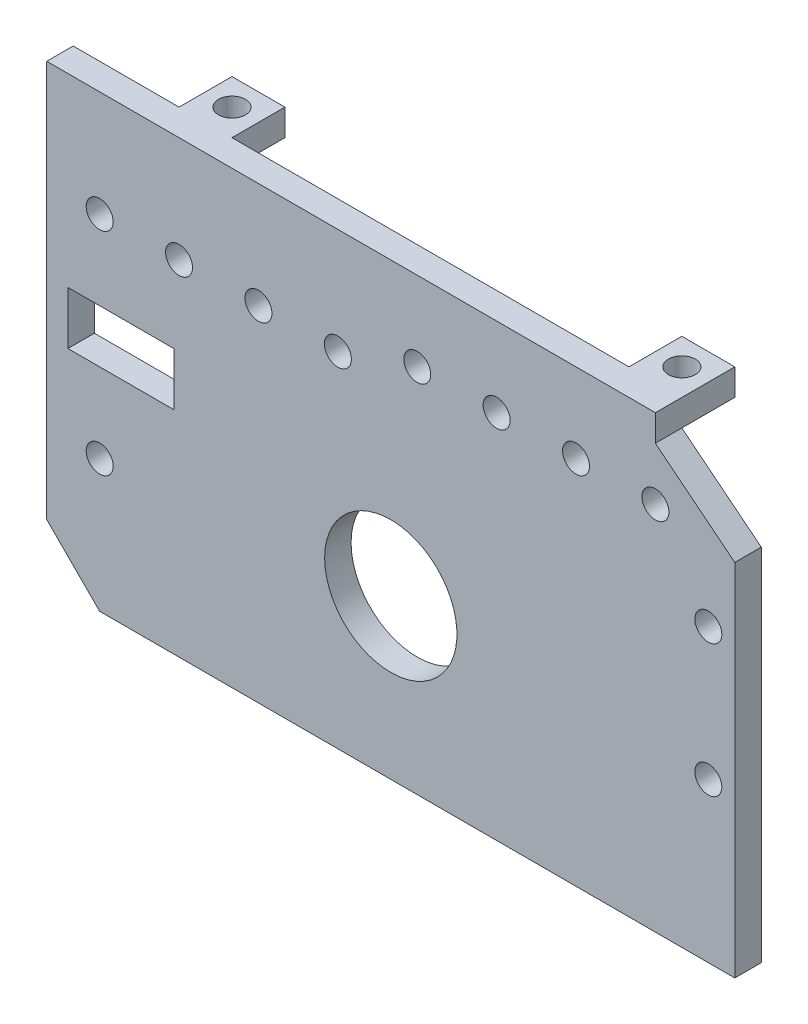
SolidWorks part; units mm, degrees
material "PLA+ esun"
ref_plane "Front Plane" through (0, 0, 0) normal (0, 0, 1) x (1, 0, 0)
ref_plane "Top Plane" through (0, 0, 0) normal (0, 1, 0) x (1, 0, 0)
ref_plane "Right Plane" through (0, 0, 0) normal (1, 0, 0) x (0, 0, -1)
sketch "Sketch1" plane through (0, 0, 0) normal (0, 0, 1) x (1, 0, 0)
  line L1 (-80, 42.5) -> (80, 42.5)
  line L2 (-80, 42.5) -> (-80, -42.5)
  line L3 (-80, -42.5) -> (80, -42.5)
  line L4 (80, 42.5) -> (80, -42.5)
  line L5 (-80, 42.5) -> (80, -42.5) construction
  line L6 (-80, -42.5) -> (80, 42.5) construction
  circle A0 centre (0, 0) radius 5
  point P0 (0, 0)
  dimension "D3" = 10
  dimension "D1" = 85
  dimension "D2" = 160
extrude "Boss-Extrude1" add sketch "Sketch1" along normal blind 5
sketch "Sketch3" plane through (0, 0, 5) normal (0, 0, 1) x (1, 0, 0)
  line L0 (-80, -42.5) -> (80, -42.5) construction
  line L1 (-80, 42.5) -> (-50, 42.5)
  line L2 (-80, 42.5) -> (-80, -42.5)
  line L3 (-80, -42.5) -> (-50, -42.5)
  line L4 (-50, 42.5) -> (-50, -42.5)
  dimension "D1" = 30
extrude "Cut-Extrude2" cut sketch "Sketch3" against normal blind 15
sketch "Sketch5" plane through (0, 0, 5) normal (0, 0, 1) x (1, 0, 0)
  line L0 (80, 42.5) -> (-50, 42.5) construction
  line L2 (80, -42.5) -> (80, 42.5) construction
  circle A0 centre (65, 27.5) radius 2.55
  circle A1 centre (50, 27.5) radius 2.55
  circle A2 centre (35, 27.5) radius 2.55
  circle A3 centre (20, 27.5) radius 2.55
  circle A8 centre (-40, 27.5) radius 2.55 [skipped]
  circle A9 centre (-25, 27.5) radius 2.55 [skipped]
  circle A10 centre (-10, 27.5) radius 2.55 [skipped]
  circle A11 centre (5, 27.5) radius 2.55 [skipped]
  circle A12 centre (5, 22.5) radius 2.55
  circle A13 centre (-10, 22.5) radius 2.55
  circle A14 centre (-25, 22.5) radius 2.55
  circle A15 centre (-40, 22.5) radius 2.55
  circle A17 centre (-40, -17.5) radius 2.55
  dimension "D1" = 5.1
  dimension "D2" = 15
  dimension "D3" = 15
  dimension "D5" = 15
  dimension "D6" = 5.1
  dimension "D7" = 15
  dimension "D8" = 20
  dimension "D10" = 2
  dimension "D4" = 8
  dimension "D9" = 4
extrude "Cut-Extrude3" cut sketch "Sketch5" against normal blind 15
chamfer "Chamfer1" distance 10 angle 45 1 edges at (-50, -42.5, 2.5)
sketch "Sketch6" plane through (0, 0, 0) normal (0, 0, -1) x (-1, 0, 0)
  line L0 (40, -42.5) -> (-80, -42.5) construction
  line L1 (-80, -42.5) -> (-65, -42.5)
  line L2 (-80, -42.5) -> (-80, -37.5)
  line L3 (-80, -37.5) -> (-65, -37.5)
  line L4 (-65, -42.5) -> (-65, -37.5)
  line L5 (-65, -37.5) -> (-55, -37.5)
  line L6 (-65, -37.5) -> (-65, -42.5)
  line L7 (-65, -42.5) -> (-55, -42.5)
  line L8 (-55, -37.5) -> (-55, -42.5)
  line L15 (50, -32.5) -> (50, 42.5) construction
  line L16 (30, -42.5) -> (20, -42.5)
  line L17 (30, -42.5) -> (30, -37.5)
  line L18 (30, -37.5) -> (20, -37.5)
  line L19 (20, -42.5) -> (20, -37.5)
  line M14 (-80, -42.5) -> (40, -42.5)
  dimension "D1" = 15
  dimension "D2" = 5
  dimension "D3" = 10
  dimension "D4" = 5
  dimension "D5" = 10
  dimension "D6" = 20
extrude "Boss-Extrude2" add sketch "Sketch6" along normal blind 10 contours L8 L5 L4 M14 | L19 L17 L18 M14 region at (-25, -40, 0) region at (60, -40, 0)
sketch "Sketch7" plane through (0, -37.5, 0) normal (0, 1, 0) x (1, 0, 0)
  line L0 (65, 10) -> (55, 10) construction
  line L1 (55, 10) -> (55, 0) construction
  line L2 (-30, 10) -> (-20, 10) construction
  line L3 (-20, 10) -> (-20, 0) construction
  circle A0 centre (60, 5) radius 2.55
  circle A1 centre (-25, 5) radius 2.55
  dimension "D1" = 5
  dimension "D2" = 5
  dimension "D3" = 5
  dimension "D4" = 5.1
  dimension "D5" = 5
  dimension "D6" = 5.1
extrude "Cut-Extrude4" cut sketch "Sketch7" against normal through all
ref_plane "Plane1" through (0, 0, 0) normal (0, 1, 0) x (1, 0, 0)
mirror "Mirror1" about plane through (0, 0, 0) normal (0, 1, 0) of "Boss-Extrude2"
mirror "Mirror2" about plane through (0, 0, 0) normal (0, 1, 0) of "Cut-Extrude4"
sketch "Sketch8" plane through (0, 0, 5) normal (0, 0, 1) x (1, 0, 0)
  line L0 (80, 42.5) -> (-50, 42.5) construction
  line L1 (80, -42.5) -> (80, 42.5) construction
  circle A0 centre (75, 12.5) radius 2.55
  circle A2 centre (75, -12.5) radius 2.55
  dimension "D1" = 5.1
  dimension "D2" = 30
  dimension "D3" = 5
  dimension "D5" = 25
  dimension "D4" = 2
extrude "Cut-Extrude5" cut sketch "Sketch8" against normal through all
sketch "Sketch9" plane through (0, 0, 5) normal (0, 0, 1) x (1, 0, 0)
  line L0 (-50, -32.5) -> (-50, 42.5) construction
  line L1 (-46, 7.5) -> (-26, 7.5)
  line L2 (-46, 7.5) -> (-46, -2.5)
  line L3 (-46, -2.5) -> (-26, -2.5)
  line L4 (-26, 7.5) -> (-26, -2.5)
  circle A0 centre (-40, 22.5) radius 2.55 construction
  circle A1 centre (-40, -17.5) radius 2.55 construction
  dimension "D1" = 15
  dimension "D2" = 15
  dimension "D3" = 4
  dimension "D4" = 20
extrude "Cut-Extrude6" cut sketch "Sketch9" against normal blind 10
sketch "Sketch10" plane through (0, 0, 5) normal (0, 0, 1) x (1, 0, 0)
  line L0 (65, 42.5) -> (65, 37.5)
  line L1 (65, 37.5) -> (80, 25.5)
  line L2 (80, -42.5) -> (80, 42.5) construction
  line L3 (80, 25.5) -> (80, 42.5)
  line L4 (80, 42.5) -> (65, 42.5)
  dimension "D1" = 17
extrude "Cut-Extrude7" cut sketch "Sketch10" against normal blind 10
sketch "Sketch11" plane through (0, 0, 0) normal (0, 0, -1) x (-1, 0, 0)
  circle A0 centre (0, 0) radius 5
extrude "Boss-Extrude3" add sketch "Sketch11" against normal blind 5
sketch "Sketch12" plane through (0, 0, 0) normal (0, 0, -1) x (-1, 0, 0)
  line L6 (-80, -42.5) -> (-80, 25.5) construction
  line L7 (-55, 42.5) -> (20, 42.5) construction
  circle A1 centre (-15, -12.5) radius 12.5
  dimension "D1" = 25
  dimension "D2" = 65
  dimension "D3" = 55
extrude "Cut-Extrude8" cut sketch "Sketch12" against normal blind 5
